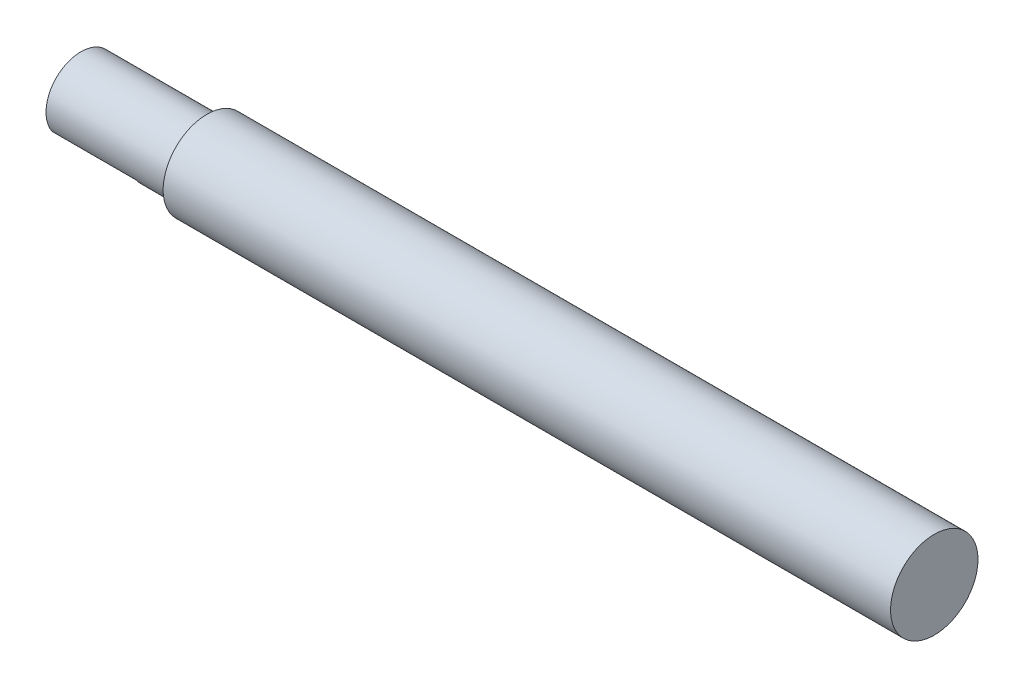
SolidWorks part; units mm, degrees
material "2024-T4"
ref_plane "Front Plane" through (0, 0, 0) normal (0, 0, 1) x (1, 0, 0)
ref_plane "Top Plane" through (0, 0, 0) normal (0, 1, 0) x (1, 0, 0)
ref_plane "Right Plane" through (0, 0, 0) normal (1, 0, 0) x (0, 0, -1)
sketch "Sketch2" plane through (0, 0, 0) normal (1, 0, 0) x (0, 0, -1)
  circle A0 centre (0, 0) radius 3.9688
  dimension "D1" = 7.9375
extrude "Boss-Extrude1" add sketch "Sketch2" along normal blind 66.04
sketch "Sketch3" plane through (0, 0, 0) normal (1, 0, 0) x (0, 0, -1)
  circle A0 centre (0, 0) radius 3.175
  dimension "D1" = 6.35
extrude "Boss-Extrude2" add sketch "Sketch3" against normal blind 11.43
sketch "Sketch4" plane through (-11.43, 0, 0) normal (-1, 0, 0) x (0, 0, 1)
  line L0 (0, 0) -> (-2.6305, -1.778) construction
  line L1 (-2.6305, -1.778) -> (2.6305, -1.778)
  line L2 (2.6305, -1.778) -> (0, 0) construction
  line L3 (0, -1.778) -> (0, 0) construction
  line L4 (-2.6305, -1.778) -> (-4.0993, -3.461)
  line L5 (-4.0993, -3.461) -> (1.3959, -3.6523)
  line L6 (1.3959, -3.6523) -> (3.0284, -2.6195)
  line L7 (3.0284, -2.6195) -> (2.6305, -1.778)
  circle A0 centre (0, 0) radius 3.175 construction
  dimension "D1" = 1.778
extrude "Cut-Extrude1" cut sketch "Sketch4" against normal blind 7.62
